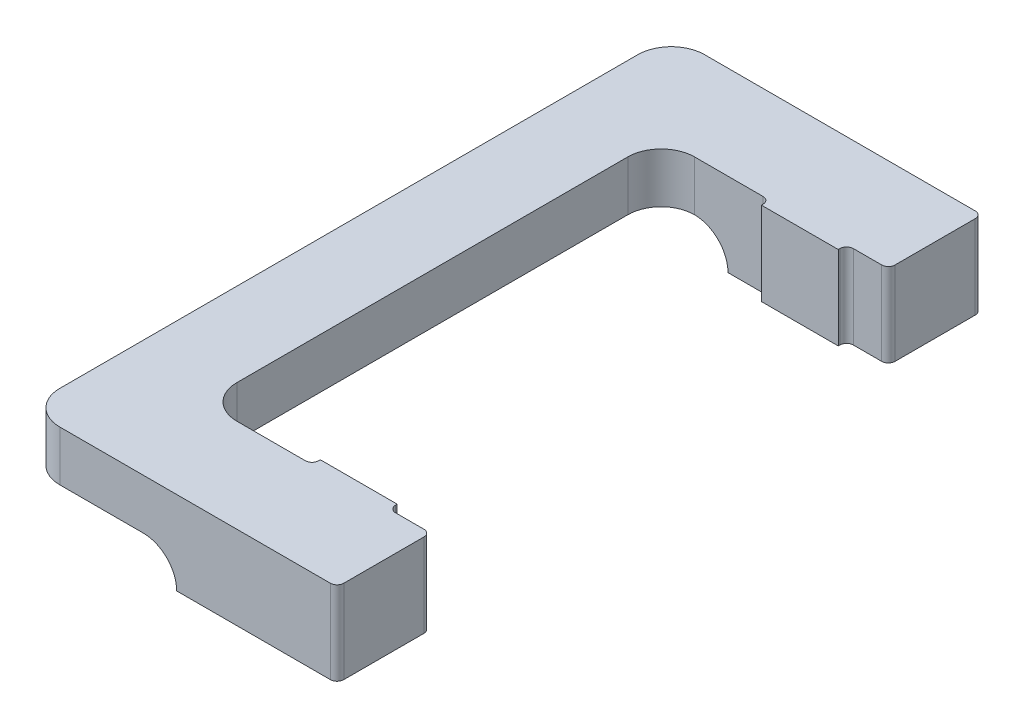
SolidWorks part; units mm, degrees
ref_plane "Front" through (0, 0, 0) normal (0, 0, 1) x (1, 0, 0)
ref_plane "Top" through (0, 0, 0) normal (0, 1, 0) x (1, 0, 0)
ref_plane "Right" through (0, 0, 0) normal (1, 0, 0) x (0, 0, -1)
sketch "Эскиз1" plane through (0, 0, 0) normal (0, 1, 0) x (1, 0, 0)
  line L0 (4.7471, 19.587) -> (-3.2529, 19.587)
  line L1 (4.7471, 19.587) -> (4.7471, 15.587)
  line L2 (4.7471, 15.587) -> (2.2471, 15.587)
  line L3 (-3.2529, 19.587) -> (-3.2529, 15.587)
  line L4 (4.7471, -13.413) -> (2.2471, -13.413)
  line L5 (4.7471, -13.413) -> (4.7471, -17.413)
  line L6 (4.7471, -17.413) -> (-3.2529, -17.413)
  line L7 (-3.2529, -13.413) -> (-3.2529, -17.413)
  line L8 (-0.7529, 15.587) -> (-3.2529, 15.587)
  line L10 (-0.7529, 15.587) -> (-0.7529, 15.087)
  line L11 (-0.7529, 15.087) -> (2.2471, 15.087)
  line L12 (2.2471, 15.587) -> (2.2471, 15.087)
  line L13 (0.7471, 19.587) -> (0.7471, -17.413) construction
  line L14 (0.7471, 1.087) -> (17.1648, 1.087) construction
  line L15 (2.2471, -13.413) -> (2.2471, -12.913)
  line L16 (-0.7529, -12.913) -> (2.2471, -12.913)
  line L17 (-0.7529, -13.413) -> (-0.7529, -12.913)
  line L18 (-0.7529, -13.413) -> (-3.2529, -13.413)
  point P8 (0.7471, 15.587)
  dimension "D1" = 8
  dimension "D3" = 3
extrude "Вытянуть-Тонкостенный1" add sketch "Эскиз1" along normal blind 5 thin thin type one direction wall 0.8
sketch "Эскиз2" plane through (0, 5, 0) normal (0, 1, 0) x (1, 0, 0)
  line L0 (-4.0529, 20.387) -> (-13.0529, 20.387)
  line L1 (-13.0529, 20.387) -> (-13.0529, -18.213)
  line L2 (-13.0529, -18.213) -> (-4.0529, -18.213)
  line L3 (-4.0529, -18.213) -> (-4.0529, -12.613)
  line L4 (-4.0529, -12.613) -> (-8.0529, -12.613)
  line L5 (-8.0529, -12.613) -> (-8.0529, 14.787)
  line L6 (-8.0529, 14.787) -> (-4.0529, 14.787)
  line L7 (-4.0529, 14.787) -> (-4.0529, 20.387)
  line L8 (-4.0529, 14.787) -> (-1.5529, 14.787) construction
  line L9 (-1.5529, -12.613) -> (-4.0529, -12.613) construction
  dimension "D1" = 5
  dimension "D2" = 9
extrude "Бобышка-Вытянуть1" add sketch "Эскиз2" against normal blind 3
sketch "Эскиз3" plane through (0, 5, 0) normal (0, 1, 0) x (1, 0, 0)
  line L1 (-3.2529, 19.587) -> (4.7471, 19.587)
  line L2 (-3.2529, 19.587) -> (-3.2529, 15.087)
  line L3 (-3.2529, 15.087) -> (4.7471, 15.087)
  line L4 (4.7471, 19.587) -> (4.7471, 15.087)
  line L5 (-3.2529, -12.913) -> (4.7471, -12.913)
  line L6 (-3.2529, -12.913) -> (-3.2529, -17.413)
  line L7 (-3.2529, -17.413) -> (4.7471, -17.413)
  line L8 (4.7471, -12.913) -> (4.7471, -17.413)
extrude "Бобышка-Вытянуть2" add sketch "Эскиз3" against normal blind 1
fillet "Скругление1" radius 2 6 edges at (-4.0529, 2, -17.587) (-4.0529, 2, 15.413) (-8.0529, 3.5, 12.613) (-8.0529, 3.5, -14.787) (-13.0529, 3.5, -20.387) (-13.0529, 3.5, 18.213)
fillet "Скругление2" radius 0.4 4 edges at (5.5471, 2.5, -20.387) (5.5471, 2.5, -14.787) (5.5471, 2.5, 12.613) (5.5471, 2.5, 18.213)
fillet "Скругление3" radius 0.4 8 edges at (3.0471, 2.5, 12.613) (-1.5529, 2.5, 12.613) (-0.7529, 2, 13.413) (2.2471, 2, 13.413) (3.0471, 2.5, -14.787) (-1.5529, 2.5, -14.787) (2.2471, 2, -15.587) (-0.7529, 2, -15.587)
